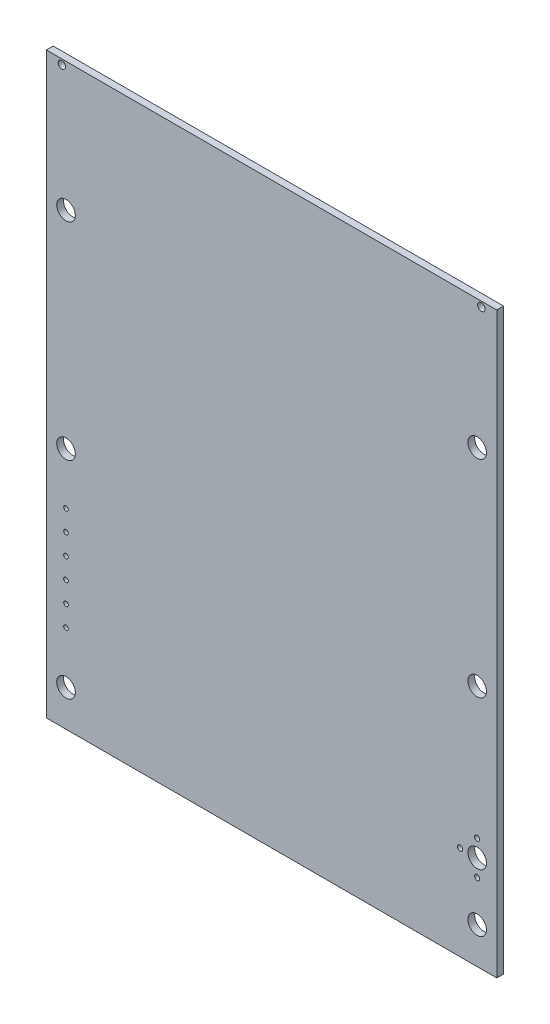
SolidWorks part; units mm, degrees
ref_plane "Front Plane" through (0, 0, 0) normal (0, 0, 1) x (1, 0, 0)
ref_plane "Top Plane" through (0, 0, 0) normal (0, 1, 0) x (1, 0, 0)
ref_plane "Right Plane" through (0, 0, 0) normal (1, 0, 0) x (0, 0, -1)
sketch "Sketch1" plane through (0, 0, 0) normal (0, 0, 1) x (1, 0, 0)
  line L0 (81.8848, 159.8822) -> (81.8848, -120.1178)
  line L1 (81.8848, 159.8822) -> (-136.1152, 159.8822)
  line L2 (81.8848, -120.1178) -> (-136.1152, -120.1178)
  line L3 (-136.1152, 159.8822) -> (-136.1152, -120.1178)
  circle A0 centre (-128.6152, 157.3822) radius 1.8
  circle A1 centre (74.3848, 157.3822) radius 1.8
  circle A2 centre (-126.6152, 97.4822) radius 4.5
  circle A3 centre (-126.6152, -2.5178) radius 4.5
  circle A4 centre (-126.6152, -102.5178) radius 4.5
  circle A5 centre (72.3848, 97.4822) radius 4.5
  circle A6 centre (72.3848, -2.5178) radius 4.5
  circle A7 centre (72.3848, -102.5178) radius 4.5
  circle A12 centre (-126.6152, -77.5178) radius 1.125
  circle A14 centre (-126.6152, -67.5178) radius 1.125
  circle A15 centre (-126.6152, -57.5178) radius 1.125
  circle A16 centre (-126.6152, -47.5178) radius 1.125
  circle A17 centre (-126.6152, -37.5178) radius 1.125
  circle A18 centre (-126.6152, -27.5178) radius 1.125
  circle A19 centre (72.3848, -74.5178) radius 4.5
  circle A21 centre (72.3848, -82.7678) radius 1.25
  circle A22 centre (64.1348, -74.5178) radius 1.25
  circle A23 centre (72.3848, -66.2678) radius 1.25
  dimension "D3" = 2.5
  dimension "D7" = 9.5
  dimension "D10" = 9.5
  dimension "D11" = 6
  dimension "D12" = 25
  dimension "D13" = 28
  dimension "D1" = 280
  dimension "D2" = 218
  dimension "D4" = 7.5
  dimension "D5" = 7.5
  dimension "D6" = 2.5
  dimension "D8" = 62.4
  dimension "D9" = 3
extrude "Boss-Extrude1" add sketch "Sketch1" along normal blind 3.302
